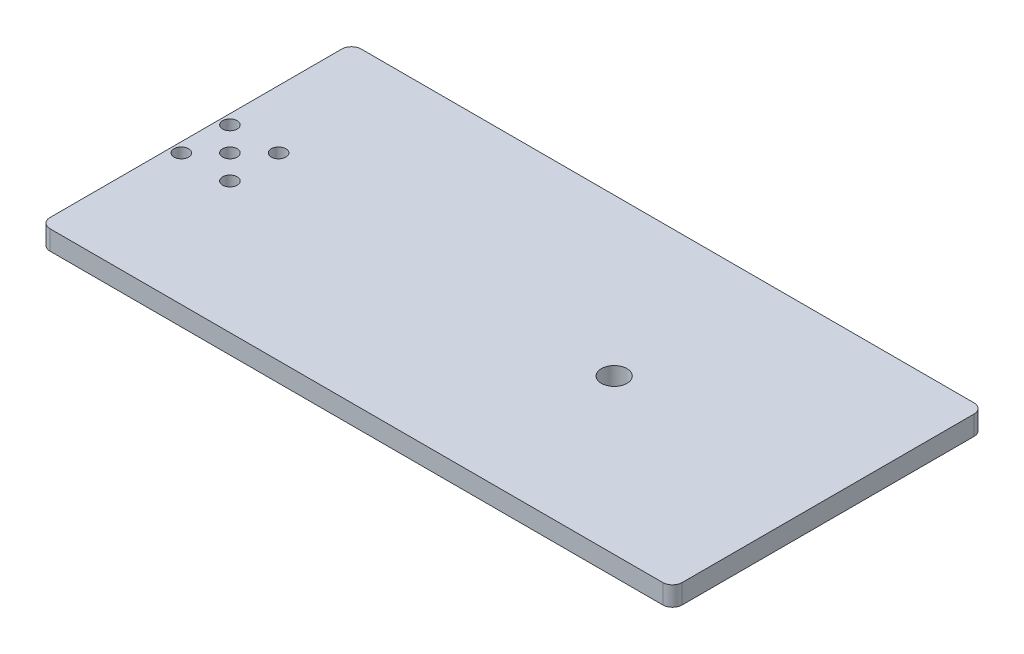
SolidWorks part; units mm, degrees
ref_plane "Front" through (0, 0, 0) normal (0, 0, 1) x (1, 0, 0)
ref_plane "Top" through (0, 0, 0) normal (0, 1, 0) x (1, 0, 0)
ref_plane "Right" through (0, 0, 0) normal (1, 0, 0) x (0, 0, -1)
sketch "Sketch1" plane through (0, 0, 0) normal (0, 1, 0) x (1, 0, 0)
  line L1 (1, 0) -> (64, 0)
  line L2 (0, 1) -> (0, 31)
  line L3 (1, 32) -> (64, 32)
  line L4 (65, 1) -> (65, 31)
  arc A0 (1, 0) -> (0, 1) centre (1, 1) cw
  arc A1 (64, 0) -> (65, 1) centre (64, 1) ccw
  arc A2 (64, 32) -> (65, 31) centre (64, 31) cw
  arc A3 (0, 31) -> (1, 32) centre (1, 31) cw
  point P7 (0, 0)
  point P10 (65, 0)
  point P13 (65, 32)
  point P16 (0, 32)
  dimension "D3" = 1
  dimension "D1" = 32
  dimension "D2" = 65
extrude "Boss-Extrude1" add sketch "Sketch1" along normal blind 2
sketch "Sketch4" plane through (65, 0, 0) normal (1, 0, 0) x (0, 0, -1)
  line L0 (1, 0) -> (31, 0) construction
  line L1 (7, 0) -> (25, 0)
  line L2 (6, 1) -> (6, 7)
  line L3 (7, 8) -> (25, 8)
  line L4 (26, 1) -> (26, 7)
  line L5 (1, 2) -> (31, 2) construction
  arc A0 (7, 0) -> (6, 1) centre (7, 1) cw
  arc A1 (25, 0) -> (26, 1) centre (25, 1) ccw
  arc A2 (25, 8) -> (26, 7) centre (25, 7) cw
  arc A3 (6, 7) -> (7, 8) centre (7, 7) cw
  point P6 (16, 2)
  point P11 (6, 0)
  point P14 (26, 0)
  point P17 (26, 8)
  point P20 (6, 8)
  dimension "D4" = 1
  dimension "D1" = 8
  dimension "D2" = 20
  dimension "D3" = 10
extrude "Boss-Extrude3" [suppressed] add sketch "Sketch4" along normal blind 2
sketch "Sketch5" [suppressed] plane through (0, 2, 0) normal (0, 1, 0) x (1, 0, 0)
  line L0 (46, 6) -> (46, 26) construction
  line L1 (46, 22) -> (44, 22)
  line L2 (46, 22) -> (46, 21.2889)
  line L3 (46, 21.2889) -> (44, 21.2889)
  line L4 (44, 22) -> (44, 21.2889)
  line L5 (46, 20) -> (46, 19.2889)
  line L6 (46, 20) -> (44, 20)
  line L7 (44, 20) -> (44, 19.2889)
  line L8 (46, 19.2889) -> (44, 19.2889)
  line L9 (46, 18) -> (46, 17.2889)
  line L10 (46, 18) -> (44, 18)
  line L11 (44, 18) -> (44, 17.2889)
  line L12 (46, 17.2889) -> (44, 17.2889)
  line L13 (46, 16) -> (46, 15.2889)
  line L14 (46, 16) -> (44, 16)
  line L15 (44, 16) -> (44, 15.2889)
  line L16 (46, 15.2889) -> (44, 15.2889)
  line L17 (46, 14) -> (46, 13.2889)
  line L18 (46, 14) -> (44, 14)
  line L19 (44, 14) -> (44, 13.2889)
  line L20 (46, 13.2889) -> (44, 13.2889)
  line L21 (46, 12) -> (46, 11.2889)
  line L22 (46, 12) -> (44, 12)
  line L23 (44, 12) -> (44, 11.2889)
  line L24 (46, 11.2889) -> (44, 11.2889)
  dimension "D2" = 2
  dimension "D3" = 4
  dimension "D1" = 6
extrude "Boss-Extrude4" [suppressed] add sketch "Sketch5" along normal blind 0.1
sketch "Sketch6" [suppressed] plane through (46, 0, 0) normal (-1, 0, 0) x (0, 0, 1)
  line L0 (-20, 2.1) -> (-20, 4.1)
  line L1 (-22, 2.1) -> (-21.2889, 2.1)
  line L2 (-22, 2.1) -> (-22, 4.1)
  line L3 (-22, 4.1) -> (-21.2889, 4.1)
  line L4 (-21.2889, 2.1) -> (-21.2889, 4.1)
  line L5 (-20, 4.1) -> (-19.2889, 4.1)
  line L6 (-19.2889, 2.1) -> (-19.2889, 4.1)
  line L7 (-20, 2.1) -> (-19.2889, 2.1)
  line L8 (-18, 2.1) -> (-18, 4.1)
  line L9 (-18, 4.1) -> (-17.2889, 4.1)
  line L10 (-17.2889, 2.1) -> (-17.2889, 4.1)
  line L11 (-18, 2.1) -> (-17.2889, 2.1)
  line L12 (-16, 2.1) -> (-16, 4.1)
  line L13 (-16, 4.1) -> (-15.2889, 4.1)
  line L14 (-15.2889, 2.1) -> (-15.2889, 4.1)
  line L15 (-16, 2.1) -> (-15.2889, 2.1)
  line L16 (-14, 2.1) -> (-14, 4.1)
  line L17 (-14, 4.1) -> (-13.2889, 4.1)
  line L18 (-13.2889, 2.1) -> (-13.2889, 4.1)
  line L19 (-14, 2.1) -> (-13.2889, 2.1)
  line L20 (-12, 2.1) -> (-12, 4.1)
  line L21 (-12, 4.1) -> (-11.2889, 4.1)
  line L22 (-11.2889, 2.1) -> (-11.2889, 4.1)
  line L23 (-12, 2.1) -> (-11.2889, 2.1)
  dimension "D1" = 2
  dimension "D2" = 6
extrude "Boss-Extrude5" [suppressed] add sketch "Sketch6" along normal blind 0.1
sketch "Sketch8" plane through (0, 2, 0) normal (0, 1, 0) x (1, 0, 0)
  line L0 (64, 32) -> (1, 32) construction
  line L1 (0, 31) -> (0, 1) construction
  circle A0 centre (3.5, 16) radius 0.75
  circle A1 centre (6, 18.5) radius 0.75
  circle A2 centre (6, 13.5) radius 0.75
  circle A3 centre (1, 13.5) radius 0.75
  circle A4 centre (1, 18.5) radius 0.75
  dimension "D1" = 1.5
  dimension "D2" = 1.5
  dimension "D3" = 1.5
  dimension "D4" = 1.5
  dimension "D5" = 1.5
  dimension "D6" = 5
  dimension "D7" = 5
  dimension "D8" = 5
  dimension "D9" = 5
  dimension "D10" = 2.5
  dimension "D11" = 2.5
  dimension "D12" = 16
  dimension "D13" = 3.5
extrude "Cut-Extrude2" cut sketch "Sketch8" against normal up to next
sketch "Sketch9" plane through (0, 2, 0) normal (0, 1, 0) x (1, 0, 0)
  circle A0 centre (43.115, 15.8909) radius 1.3165
extrude "Cut-Extrude3" cut sketch "Sketch9" against normal up to next
